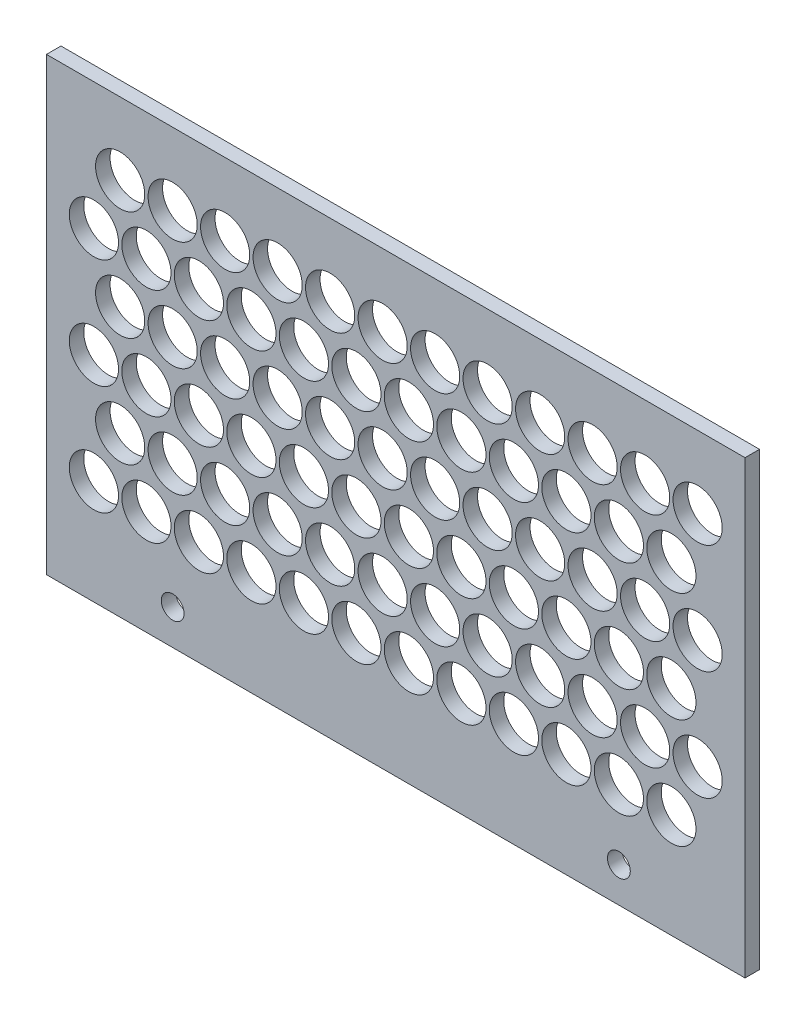
SolidWorks part; units mm, degrees
material "ABS"
ref_plane "X-Y Datum" through (0, 0, 0) normal (0, 0, 1) x (1, 0, 0)
ref_plane "X-Z Datum" through (0, 0, 0) normal (0, 1, 0) x (1, 0, 0)
ref_plane "Y-Z Datum" through (0, 0, 0) normal (1, 0, 0) x (0, 0, -1)
sketch "Sketch1" plane through (0, 0, 0) normal (0, 0, 1) x (1, 0, 0)
  line L1 (-143.025, 70.775) -> (143.025, 70.775)
  line L2 (-143.025, 70.775) -> (-143.025, -70.775)
  line L3 (-143.025, -70.775) -> (143.025, -70.775)
  line L4 (143.025, 70.775) -> (143.025, -70.775)
  line L5 (-143.025, 70.775) -> (143.025, -70.775) construction
  line L6 (-143.025, -70.775) -> (143.025, 70.775) construction
  line L13 (-153.025, -105.775) -> (153.025, -105.775)
  line L14 (-153.025, 91.65) -> (153.025, 91.65)
  line L15 (-153.025, 91.65) -> (-153.025, -105.775)
  line L16 (153.025, 91.65) -> (153.025, -105.775)
  line L17 (153.025, 70.775) -> (153.025, -70.775) construction
  line L18 (-143.025, 91.65) -> (143.025, 91.65) construction
  line L19 (-143.025, -105.775) -> (143.025, -105.775) construction
  line L20 (-153.025, 70.775) -> (-153.025, -70.775) construction
  line L21 (-132.25, -60) -> (-109.25, -60) construction
  circle A0 centre (-132.25, -60) radius 10.775
  circle A1 centre (-109.25, -60) radius 10.775 construction
  circle A2 centre (-120.75, -36) radius 10.775
  point P0 (0, 0)
  point P16 (-120.75, -60)
  dimension "D1" = 21.55
  dimension "D2" = 23
  dimension "D3" = 24
  dimension "D5" = 141.55
  dimension "D6" = 286.05
  dimension "D7" = 35
  dimension "D8" = 20.875
  dimension "D9" = 10
  dimension "D10" = 10
extrude "Boss-Extrude1" add sketch "Sketch1" along normal blind 6.35 contours A0 L3 L4 L1 L2 A2 | A2 | A0 | A0 L2 L3 | L1 L4 L3 L2 region at (2.4105, 0.9241, 0) region at (-140.6182, -68.3682, 0) region at (-132.25, -60, 0) region at (-149.383, -7.0625, 0) region at (-120.75, -36, 0)
sketch "Sketch3" plane through (0, 0, 6.35) normal (0, 0, 1) x (1, 0, 0)
  line L4 (143.025, 70.775) -> (-143.025, 70.775)
  line L5 (143.025, -70.775) -> (143.025, 70.775)
  line L6 (-143.025, -70.775) -> (143.025, -70.775)
  line L7 (-143.025, 70.775) -> (-143.025, -70.775)
  line L8 (143.025, 70.775) -> (-143.025, 70.775)
  line L9 (143.025, -70.775) -> (143.025, 70.775)
  line L10 (-143.025, -70.775) -> (143.025, -70.775)
  line L11 (-143.025, 70.775) -> (-143.025, -70.775)
  circle A1 centre (-120.75, -36) radius 10.775
  circle A2 centre (-120.75, -36) radius 10.775
  circle A3 centre (-132.25, -60) radius 10.775
  circle A4 centre (-132.25, -60) radius 10.775
  dimension "D1" = 0
  dimension "D2" = 0
  dimension "D3" = 0
extrude "Cut-Extrude1" cut sketch "Sketch3" against normal through all contours A4 region at (-132.25, -60, 6.35)
sketch "Sketch4" plane through (0, 0, 6.35) normal (0, 0, 1) x (1, 0, 0)
  line L4 (143.025, 70.775) -> (-143.025, 70.775)
  line L5 (143.025, -70.775) -> (143.025, 70.775)
  line L6 (-143.025, -70.775) -> (143.025, -70.775)
  line L7 (-143.025, 70.775) -> (-143.025, -70.775)
  line L8 (143.025, 70.775) -> (-143.025, 70.775)
  line L9 (143.025, -70.775) -> (143.025, 70.775)
  line L10 (-143.025, -70.775) -> (143.025, -70.775)
  line L11 (-143.025, 70.775) -> (-143.025, -70.775)
  circle A1 centre (-120.75, -36) radius 10.775
  circle A2 centre (-120.75, -36) radius 10.775
  circle A3 centre (-132.25, -60) radius 10.775
  circle A4 centre (-132.25, -60) radius 10.775
  dimension "D1" = 0
  dimension "D2" = 0
  dimension "D3" = 0
extrude "Cut-Extrude2" cut sketch "Sketch4" against normal through all contours A2 region at (-120.75, -36, 6.35)
pattern_linear "LPattern1" count 12 spacing 23 along (1, 0, 0) of "Cut-Extrude1", "Cut-Extrude2"
pattern_linear "LPattern2" count 3 spacing 48 along (0, 1, 0) of "LPattern1"
sketch "Sketch5" plane through (0, 0, 0) normal (0, 0, -1) x (-1, 0, 0)
  circle A0 centre (-97.75, -90.3965) radius 2 construction
  circle A1 centre (-97.75, -90.3965) radius 2 construction
  circle A2 centre (-97.75, -90.3965) radius 5
  dimension "D1" = 10
extrude "Cut-Extrude3" cut sketch "Sketch5" against normal through all
mirror "Mirror1" about plane through (0, 0, 0) normal (1, 0, 0) of "Cut-Extrude3"
